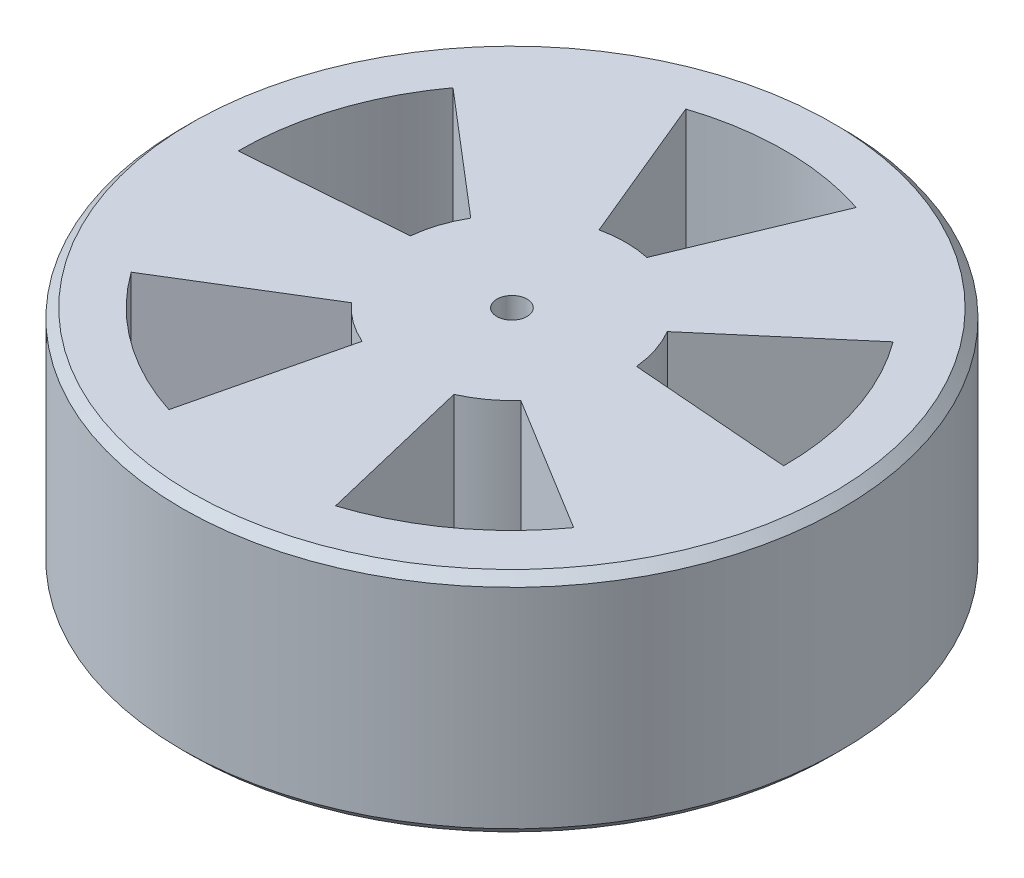
SolidWorks part; units mm, degrees
ref_plane "Front Plane" through (0, 0, 0) normal (0, 0, 1) x (1, 0, 0)
ref_plane "Top Plane" through (0, 0, 0) normal (0, 1, 0) x (1, 0, 0)
ref_plane "Right Plane" through (0, 0, 0) normal (1, 0, 0) x (0, 0, -1)
sketch "Sketch2" plane through (0, 0, 0) normal (0, 1, 0) x (1, 0, 0)
  circle A0 centre (0, 0) radius 73.66
  dimension "D1" = 147.32
extrude "Boss-Extrude1" add sketch "Sketch2" along normal blind 50.8
chamfer "Chamfer1" distance 2.032 angle 45 2 edges at (0, 0, 73.66) (0, 50.8, 73.66)
sketch "Sketch3" plane through (0, 50.8, 0) normal (0, 1, 0) x (1, 0, 0)
  line L0 (-12.7, 0) -> (0, 0) construction
  line L1 (0, 0) -> (12.7, 0) construction
  circle A0 centre (0, 0) radius 25.4 construction
  circle A1 centre (-12.7, 0) radius 3.175
  circle A2 centre (12.7, 0) radius 3.175
  dimension "D1" = 6.35
  dimension "D4" = 50.8
  dimension "D2" = 12.7
  dimension "D3" = 12.7
extrude "Cut-Extrude1" [suppressed] cut sketch "Sketch3" against normal through all both and the other way through all
sketch "Sketch4" plane through (0, 50.8, 0) normal (0, 1, 0) x (1, 0, 0)
  line L0 (0, 25.4) -> (0, 60.96) construction
  line L1 (-5.3492, 24.8303) -> (-19.05, 57.907)
  line L2 (5.3492, 24.8303) -> (19.05, 57.907)
  line L3 (21.9621, 12.7604) -> (49.186, 36.0119)
  line L4 (25.2681, 2.5856) -> (60.9596, -0.2234)
  line L5 (18.9225, -16.944) -> (49.4486, -35.6504)
  line L6 (10.2673, -23.2324) -> (18.6251, -58.045)
  line L7 (-10.2673, -23.2324) -> (-18.6251, -58.045)
  line L8 (-18.9225, -16.944) -> (-49.4486, -35.6504)
  line L9 (-25.2681, 2.5856) -> (-60.9596, -0.2234)
  line L10 (-21.9621, 12.7604) -> (-49.186, 36.0119)
  arc A0 (5.3492, 24.8303) -> (-5.3492, 24.8303) centre (0, 0) ccw
  arc A7 (-19.05, 57.907) -> (19.05, 57.907) centre (0, 0) cw
  circle A9 centre (0, 0) radius 73.66 construction
  arc A20 (25.2681, 2.5856) -> (21.9621, 12.7604) centre (0, 0) ccw
  arc A21 (60.9596, -0.2234) -> (49.186, 36.0119) centre (0, 0) ccw
  arc A22 (10.2673, -23.2324) -> (18.9225, -16.944) centre (0, 0) ccw
  arc A23 (18.6251, -58.045) -> (49.4486, -35.6504) centre (0, 0) ccw
  arc A24 (-18.9225, -16.944) -> (-10.2673, -23.2324) centre (0, 0) ccw
  arc A25 (-49.4486, -35.6504) -> (-18.6251, -58.045) centre (0, 0) ccw
  arc A26 (-21.9621, 12.7604) -> (-25.2681, 2.5856) centre (0, 0) ccw
  arc A27 (-49.186, 36.0119) -> (-60.9596, -0.2234) centre (0, 0) ccw
  point P30 (0, 0)
  point P32 (0, 0)
  dimension "D1" = 50.8
  dimension "D2" = 12.7
  dimension "D3" = 22.5
  dimension "D4" = 45
  dimension "D5" = 19.05
  dimension "D6" = 19.05
  dimension "D7" = 5
extrude "Cut-Extrude2" cut sketch "Sketch4" against normal through all both and the other way through all contours L9 A27 L10 A26 | L7 A25 L8 A24 | L5 A23 L6 A22 | L3 A21 L4 A20 | A7 L2 A0 L1
sketch "Sketch5" plane through (0, 50.8, 0) normal (0, 1, 0) x (1, 0, 0)
  point P0 (0, 0)
hole_wizard "1/4 Clearance Hole1" positions "Sketch5" profile "Sketch6" hole size "1/4" standard "ANSI Inch" end condition through all
sketch "Sketch6" plane through (0, 50.8, 0) normal (1, 0, 0) x (0, 0, 1)
  line L0 (0, 0) -> (0, 50.8)
  line L1 (0, 50.8) -> (3.3782, 50.8)
  line L2 (3.3782, 50.8) -> (3.3782, 0)
  line L5 (3.3782, 0) -> (0, 0)
  line L11 (0, -6.35) -> (0, 107.95) construction
  dimension "Thru Hole Dia." = 6.7564
  dimension "Thru Hole Depth" = 50.8
equation "\"OD\"= 5.820"
equation "\"offset\" = 0.02"
equation "\"L\"= 2"
equation "\"ID\"= 3"
equation "\"D1@Sketch2\"=\"OD\"-\"offset\""
equation "\"D1@Boss-Extrude1\"=\"L\""
